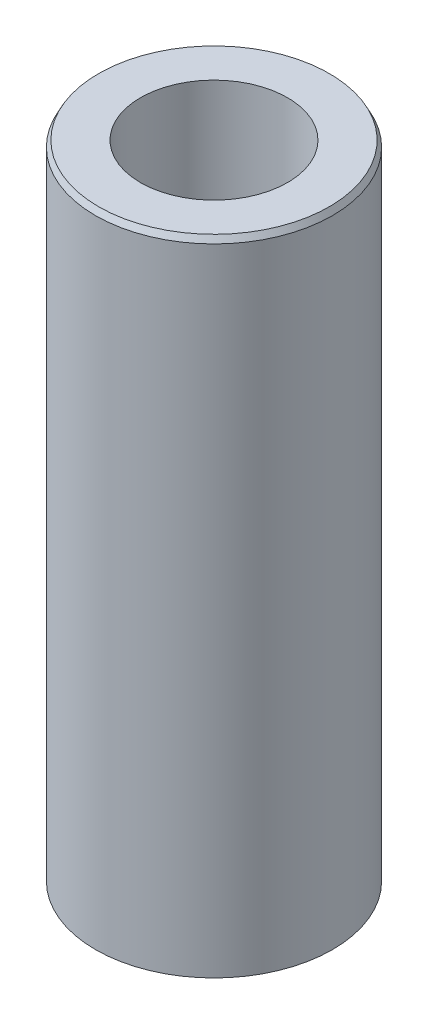
SolidWorks part; units mm, degrees
ref_plane "Front Plane" through (0, 0, 0) normal (0, 0, 1) x (1, 0, 0)
ref_plane "Top Plane" through (0, 0, 0) normal (0, 1, 0) x (1, 0, 0)
ref_plane "Right Plane" through (0, 0, 0) normal (1, 0, 0) x (0, 0, -1)
sketch "Sketch1" plane through (0, 0, 0) normal (0, 1, 0) x (1, 0, 0)
  circle A0 centre (0, 0) radius 52.5
  dimension "SHAFT_OD" = 105
extrude "Boss-Extrude1" add sketch "Sketch1" along normal blind 285.6697
sketch "Sketch2" plane through (0, 0, 0) normal (0, 1, 0) x (1, 0, 0)
  circle A0 centre (0, 0) radius 32.5802
  dimension "BORE_D" = 65.1604
extrude "Cut-Extrude1" cut sketch "Sketch2" along normal through all
chamfer "Chamfer1" distance 2.7052 angle 27.401 2 edges at (0, 285.6697, 52.5) (0, 0, 52.5) first distance on face at (0, 285.6697, 52.5) first distance on face at (0, 0, 32.5802)
